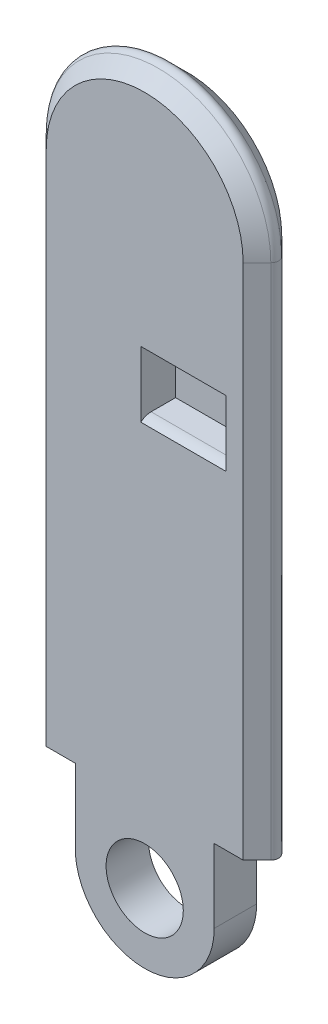
SolidWorks part; units mm, degrees
ref_plane "Płaszczyzna przednia" through (0, 0, 0) normal (0, 0, 1) x (1, 0, 0)
ref_plane "Płaszczyzna górna" through (0, 0, 0) normal (0, 1, 0) x (1, 0, 0)
ref_plane "Płaszczyzna prawa" through (0, 0, 0) normal (1, 0, 0) x (0, 0, -1)
sketch "Szkic1" plane through (0, 0, 0) normal (0, 0, 1) x (1, 0, 0)
  line L1 (-15.75, 33.5) -> (15.75, 33.5)
  line L2 (-15.75, 33.5) -> (-15.75, -33.5)
  line L3 (-15.75, -33.5) -> (15.75, -33.5)
  line L4 (15.75, 33.5) -> (15.75, -33.5)
  line L5 (-15.75, 33.5) -> (15.75, -33.5) construction
  line L6 (-15.75, -33.5) -> (15.75, 33.5) construction
  circle A0 centre (0, 33.5) radius 15.75
  point P0 (0, 0)
  dimension "D1" = 31.5
  dimension "D2" = 67
extrude "Dodanie-wyciągnięcie1" add sketch "Szkic1" against normal blind 6 contours L1 A0 | L1 A0 | A0 L2 L3 L4 region at (0, 40.1845, 0) region at (0, -6.0719, 0) region at (0, 26.8155, 0)
chamfer "Sfazowanie1" distance 3.5 angle 45 6 edges at (15.75, 0, -6) (0, 49.25, -6) (-15.75, 0, -6) (15.75, 0, 0) (0, 49.25, 0) (-15.75, 0, 0)
fillet "Zaokrąglenie1" radius 1 3 edges at (15.25, 0, -3) (0, 48.75, -3) (-15.25, 0, -3)
sketch "Szkic2" plane through (0, 0, 0) normal (0, 0, 1) x (1, 0, 0)
  line L0 (-0.5, 12.25) -> (10.5, 12.25) construction
  line L1 (-10.6279, -13.75) -> (-5.9102, -13.75) construction
  line L10 (-0.5, 15) -> (-0.5, 9.5)
  line L11 (10.5, 9.5) -> (10.5, 15)
  line L12 (-0.5, 15) -> (10.5, 15)
  line L13 (-0.5, 9.5) -> (10.5, 9.5)
  line L14 (5, 15) -> (5, 9.5) construction
  point P15 (-8.269, -13.75)
  dimension "D1" = 5.5
  dimension "D2" = 11
  dimension "D3" = 5
  dimension "D4" = 13.75
  dimension "D5" = 26
extrude "Wytnij-wyciągnięcie1" cut sketch "Szkic2" against normal blind 5
sketch "Szkic3" plane through (0, 0, -6) normal (0, 0, -1) x (-1, 0, 0)
  line L2 (6, -24) -> (6, -27.9889) construction
  line L4 (1.5, -31.2389) -> (10.5, -31.2389)
  line L5 (1.5, -31.2389) -> (1.5, -24.7389)
  line L6 (1.5, -24.7389) -> (10.5, -24.7389)
  line L7 (10.5, -31.2389) -> (10.5, -24.7389)
  line L8 (1.5, -31.2389) -> (10.5, -24.7389) construction
  line L9 (1.5, -24.7389) -> (10.5, -31.2389) construction
  dimension "D2" = 9
  dimension "D3" = 6.5
extrude "Wytnij-wyciągnięcie2" cut sketch "Szkic3" against normal blind 4.5
chamfer "Sfazowanie2" distance 0.5 angle 45 1 edges at (-6, -24.7389, -6)
sketch "Szkic4" plane through (0, 0, 0) normal (0, 0, 1) x (1, 0, 0)
  line L0 (0, -33.5) -> (0, -43.0308) construction
  line L1 (-12.25, -33.5) -> (12.25, -33.5) construction
  line L2 (9, -43.0308) -> (9, -33.5)
  line L3 (9, -33.5) -> (-8.9747, -33.5)
  line L4 (-8.9747, -33.5) -> (-8.9747, -43.7054)
  circle A0 centre (0, -43.0308) radius 5
  circle A1 centre (0, -43.0308) radius 9
  line M6 (-12.25, -33.5) -> (12.25, -33.5)
  dimension "D1" = 4
  dimension "D2" = 10
extrude "Dodanie-wyciągnięcie2" add sketch "Szkic4" against normal blind 6 contours L3 L0 A1 L2 | A1 A0 L4 | L0 L4 A1 M6 region at (6.4529, -35.5505, 0) region at (-6.4264, -35.5244, 0) region at (6.1841, -36.8467, 0)
sketch "Szkic5" plane through (0, 0, -6) normal (0, 0, -1) x (-1, 0, 0)
  line L3 (-5, 16) -> (0, 16)
  line L4 (0, 16) -> (0, -31)
  line L5 (-5, -31) -> (-5, 16)
  line L6 (-2.5, 16) -> (-2.5, -22.2858) construction
  line L8 (-0.5, 15) -> (-4.5, 15)
  line L9 (-0.5, 15) -> (-0.5, 9)
  line L10 (-0.5, 9) -> (-4.5, 9)
  line L11 (-4.5, 15) -> (-4.5, 9)
  line L12 (-0.5, 15) -> (-4.5, 9) construction
  line L13 (-0.5, 9) -> (-4.5, 15) construction
  point P6 (-2.5, 12)
  dimension "D1" = 1
  dimension "D2" = 0.5
  dimension "D3" = 6
  dimension "D4" = 5
  dimension "D5" = 16
  dimension "D6" = 2.5
extrude "Dodanie-wyciągnięcie3" add sketch "Szkic5" along normal blind 4.5 contours L8 L11 L10 L9 region at (2.5, 12, -6)
chamfer "Sfazowanie3" distance 3 angle 45 1 edges at (5, 15, 0)
chamfer "Sfazowanie4" distance 1 angle 45 1 edges at (5, 9.5, 0)
fillet "Zaokrąglenie2" radius 2 1 edges at (5, 9.5, -1)
sketch "Szkic6" plane through (0, 0, 0) normal (0, 0, 1) x (1, 0, 0)
  line L1 (-24.2232, 57.0446) -> (24.2232, 57.0446)
  line L2 (-24.2232, 57.0446) -> (-24.2232, -57.0446)
  line L3 (-24.2232, -57.0446) -> (24.2232, -57.0446)
  line L4 (24.2232, 57.0446) -> (24.2232, -57.0446)
  line L5 (-24.2232, 57.0446) -> (24.2232, -57.0446) construction
  line L6 (-24.2232, -57.0446) -> (24.2232, 57.0446) construction
  point P0 (0, 0)
extrude "Wytnij-wyciągnięcie3" cut sketch "Szkic6" against normal blind 0.5
